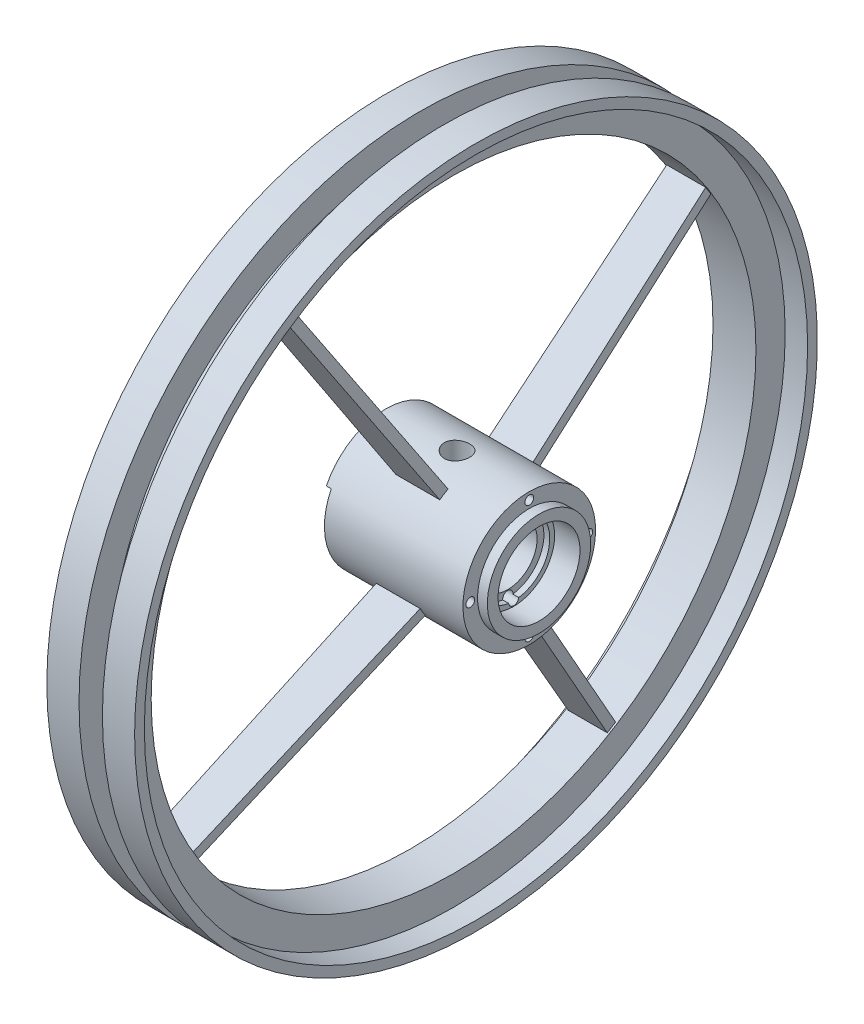
SolidWorks part; units mm, degrees
ref_plane "Front Plane" through (0, 0, 0) normal (0, 0, 1) x (1, 0, 0)
ref_plane "Top Plane" through (0, 0, 0) normal (0, 1, 0) x (1, 0, 0)
ref_plane "Right Plane" through (0, 0, 0) normal (1, 0, 0) x (0, 0, -1)
sketch "Sketch17" plane through (0, 0, 0) normal (0, 0, 1) x (1, 0, 0)
  line L0 (0, 0) -> (156.5215, 0) construction
sketch "Sketch1" plane through (0, 0, 0) normal (1, 0, 0) x (0, 0, -1)
  circle A0 centre (0, 0) radius 68
extrude "Boss-Extrude1" add sketch "Sketch1" along normal blind 157 contours A0
sketch "Sketch2" plane through (0, 0, 0) normal (-1, 0, 0) x (0, 0, 1)
  circle A0 centre (0, 0) radius 26
extrude "Cut-Extrude1" cut sketch "Sketch2" against normal up to next
sketch "Sketch3" plane through (0, 0, 0) normal (-1, 0, 0) x (0, 0, 1)
  line L1 (-68, 30) -> (68, 30)
  line L2 (-68, 30) -> (-68, -68)
  line L3 (-68, -68) -> (68, -68)
  line L4 (68, 30) -> (68, -68)
  circle A2 centre (0, 0) radius 68 construction
  circle A3 centre (0, 0) radius 26 construction
  dimension "D1" = 30
  dimension "D2" = 68
  dimension "D3" = 42
  dimension "D4" = 68
  dimension "D5" = 68
extrude "Cut-Extrude2" cut sketch "Sketch3" against normal blind 5 contours L2 L3 L4 L1
sketch "Sketch4" plane through (5, 0, 0) normal (-1, 0, 0) x (0, 0, 1)
  line L3 (-13.5, 29) -> (13.5, 29)
  arc A2 (13.5, 29) -> (-13.5, 29) centre (0, 0) cw
  dimension "D1" = 27
  dimension "D2" = 29
extrude "Cut-Extrude3" cut sketch "Sketch4" against normal blind 44
sketch "Sketch7" plane through (157, 0, 0) normal (1, 0, 0) x (0, 0, -1)
  circle A0 centre (0, 0) radius 42
extrude "Cut-Extrude4" cut sketch "Sketch7" against normal blind 26
sketch "Sketch8" plane through (131, 0, 0) normal (1, 0, 0) x (0, 0, -1)
  circle A0 centre (0, 0) radius 37
extrude "Cut-Extrude5" cut sketch "Sketch8" against normal blind 6 contours A0
sketch "Sketch9" plane through (125, 0, 0) normal (1, 0, 0) x (0, 0, -1)
  circle A0 centre (0, 0) radius 30
extrude "Cut-Extrude6" cut sketch "Sketch9" against normal blind 28 contours A0
ref_plane "Plane2" through (0, 0, 68) normal (0, 0, 1) x (1, 0, 0)
sketch "Sketch12" plane through (0, 0, 68) normal (0, 0, 1) x (1, 0, 0)
  line L0 (49, 37.9633) -> (49, -31.4216)
  line L1 (49, -31.4216) -> (59.8739, -42.2955)
  line L2 (59.8739, -42.2955) -> (85.8739, -42.2955)
  line L3 (85.8739, -42.2955) -> (97, -31.1695)
  line L4 (97, -31.1695) -> (97, 37.7112)
  line L5 (97, 37.7112) -> (85.8739, 48.8372)
  line L6 (85.8739, 48.8372) -> (59.8739, 48.8372)
  line L7 (59.8739, 48.8372) -> (49, 37.9633)
  line L8 (157, -68) -> (157, 68) construction
  line L9 (5, 30) -> (5, -68) construction
  dimension "D1" = 60
  dimension "D2" = 44
  dimension "D3" = 26
  dimension "D4" = 26
  dimension "D5" = 135
  dimension "D6" = 135
  dimension "D7" = 135
  dimension "D8" = 135
sketch "Sketch16" plane through (0, 0, 0) normal (-1, 0, 0) x (0, 0, 1)
  line L0 (35.9404, 57.726) -> (61.0246, 30) construction
  line L1 (35.9404, 57.726) -> (0, 68) construction
  arc A0 (61.0246, 30) -> (-61.0246, 30) centre (0, 0) ccw construction
  dimension "D1" = 37.38
  dimension "D2" = 37.3892
ref_plane "Plane5" through (0, 68, 0) normal (0, 1, 0) x (1, 0, 0)
ref_plane "Plane7" through (0, 0, 0) normal (0, 0, 1) x (1, 0, 0)
sketch "Sketch23" plane through (0, 68, 0) normal (0, 1, 0) x (1, 0, 0)
  line L0 (86, -40) -> (86, 40) construction
  point P9 (73, 0)
  dimension "D1" = 13
sketch "Sketch27" plane through (157, 0, 0) normal (1, 0, 0) x (0, 0, -1)
  circle A0 centre (0, 0) radius 68
  circle A1 centre (0, 0) radius 53
  dimension "D1" = 136
  dimension "D2" = 106
extrude "Cut-Extrude9" cut sketch "Sketch27" against normal blind 10
sketch "Sketch36" plane through (0, 0, 0) normal (0, 0, 1) x (1, 0, 0)
  line L0 (49, 29) -> (60, 40)
  line L1 (60, 40) -> (86, 40)
  line L2 (86, 40) -> (97, 29)
  line L8 (147, 68) -> (0, 68) construction
  line L17 (49, 29) -> (49, 0)
  line L18 (0, 0) -> (156.5215, 0) construction
  line L19 (49, 0) -> (97, 0)
  line L20 (97, 0) -> (97, 29)
  line L21 (157, -53) -> (157, 53) construction
  line L22 (5, 30) -> (5, -68) construction
  dimension "D1" = 60
  dimension "D2" = 44
  dimension "D3" = 135
  dimension "D4" = 40
  dimension "D5" = 26
revolve "Cut-Revolve2" cut sketch "Sketch36" angle 360 about L0
hole_wizard "Tap Drill for M1.2x0.25 Tap1" positions "Sketch23" profile "Sketch26" hole size "M1.2x0.25" standard "ISO"
sketch "Sketch26" plane through (73, 68, 0) normal (1, 0, 0) x (0, 0, 1)
  line L0 (0, 0) -> (0, 68)
  line L1 (0, 68) -> (13, 68)
  line L2 (13, 68) -> (13, 0)
  line L5 (13, 0) -> (0, 0)
  line L10 (0, 68) -> (-13, 68) construction
  line L11 (0, -6.35) -> (0, 107.95) construction
  dimension "Hole Dia." = 26
  dimension "Hole Depth" = 68
  dimension "Drill Angle" = 180
sketch "Sketch29" plane through (147, 0, 0) normal (1, 0, 0) x (0, 0, -1)
  line L0 (0, 68) -> (0, 53) construction
  line L1 (53, 0) -> (68, 0) construction
  line L2 (0, -53) -> (0, -68) construction
  line L3 (-53, 0) -> (-68, 0) construction
  line L4 (-68, 74.8) -> (-68, -74.8) construction
  circle A0 centre (0, 0) radius 53 construction
  circle A1 centre (0, 0) radius 53 construction
  circle A2 centre (0, 0) radius 68 construction
  point P21 (0, 60.5)
  point P23 (60.5, 0)
  point P25 (0, -60.5)
  point P27 (-60.5, 0)
hole_wizard "M8 Clearance Hole1" positions "Sketch29" profile "Sketch30" hole size "M8" standard "ISO"
sketch "Sketch30" plane through (147, 0, 60.5) normal (0, 1, 0) x (0, 0, -1)
  line L0 (0, 0) -> (0, 37.7039)
  line L1 (0, 37.7039) -> (4.5, 35)
  line L2 (4.5, 35) -> (4.5, 0)
  line L5 (4.5, 0) -> (0, 0)
  line L10 (0, 37.7039) -> (-4.5, 35) construction
  line L11 (0, -6.35) -> (0, 107.95) construction
  dimension "Hole Dia." = 9
  dimension "Hole Depth" = 35
  dimension "Drill Angle" = 118
ref_plane "Plane4" through (0, 0, 0) normal (0, 0.5285, -0.8489) x (-1, 0, 0)
sketch "Sketch19" plane through (0, 0, 0) normal (0, 0.5285, -0.8489) x (-1, 0, 0)
  line L1 (-97, 30) -> (-97, -30) construction
  line L3 (-27.3689, 310) -> (-67.3689, 310)
  line L9 (0, 0) -> (-156.5215, 0) construction
  line L10 (-67.3689, 310) -> (-95.5, 66.5)
  line L11 (-95.5, 66.5) -> (-50.5, 66.5)
  line L12 (-50.5, 66.5) -> (-27.3689, 310)
  line L13 (0, 68) -> (-147, 68) construction
  dimension "D1" = 310
  dimension "D2" = 83.41
  dimension "D3" = 45
  dimension "D4" = 1.5
  dimension "D5" = 1.5
  dimension "D6" = 40
sketch "Sketch21" plane through (0, 0, 0) normal (0, 0.5285, -0.8489) x (-1, 0, 0)
  line L0 (-67.3689, 310) -> (-69.3689, 310)
  line L1 (-69.3689, 310) -> (-69.3689, 340)
  line L2 (-69.3689, 340) -> (-92.3689, 340)
  line L3 (-92.3689, 340) -> (-92.3689, 350)
  line L4 (-92.3689, 350) -> (-59.3689, 350)
  line L5 (-2.3689, 350) -> (-2.3689, 340)
  line L6 (-2.3689, 340) -> (-25.3689, 340)
  line L7 (-25.3689, 340) -> (-25.3689, 310)
  line L8 (-25.3689, 310) -> (-27.3689, 310)
  line L11 (-59.3689, 350) -> (-59.3689, 320)
  line L12 (-59.3689, 320) -> (-35.3689, 320)
  line L13 (-35.3689, 320) -> (-35.3689, 350)
  line L14 (-35.3689, 350) -> (-2.3689, 350)
  line L15 (-27.3689, 310) -> (-67.3689, 310) construction
  line L17 (-67.3689, 310) -> (-27.3689, 310)
  dimension "D2" = 10
  dimension "D3" = 10
  dimension "D7" = 10
  dimension "D8" = 90
  dimension "D11" = 40
  dimension "D12" = 40
  dimension "D10" = 2
  dimension "D5" = 2
  dimension "D6" = 10
  dimension "D9" = 10
  dimension "D4" = 23
  dimension "D13" = 24
revolve "Revolve1" add sketch "Sketch21" angle 360 about L0
extrude "Boss-Extrude4" add sketch "Sketch19" along normal mid plane 10
pattern_circular "CirPattern4" count 4 every 90 about axis through (0, 0, 0) along (1, 0, 0) of "Boss-Extrude4"
sketch "Esquisse4" plane through (131, 0, 0) normal (1, 0, 0) x (0, 0, -1)
  line L0 (0, 0) -> (0, -36) construction
  point P11 (0, -36)
  dimension "D1" = 36
  dimension "D2" = 0
hole_wizard "M10 Clearance Hole1" positions "Esquisse4" profile "Esquisse6" hole size "M10" standard "ANSI Metric"
sketch "Esquisse6" plane through (131, -36, 0) normal (0, 1, 0) x (0, 0, -1)
  line L0 (0, 0) -> (0, 15)
  line L1 (0, 15) -> (5.25, 15)
  line L2 (5.25, 15) -> (5.25, 0)
  line L5 (5.25, 0) -> (0, 0)
  line L10 (0, 15) -> (-5.25, 15) construction
  line L11 (0, -6.35) -> (0, 107.95) construction
  dimension "Hole Dia." = 10.5
  dimension "Hole Depth" = 15
  dimension "Drill Angle" = 180
equation "\"D1@Sketch3\"=26+8/2"
equation "\"D2@Sketch3\"=26+\"D3@Sketch3\""
equation "\"D4@Sketch3\"=\"D2@Sketch3\""
equation "\"D5@Sketch3\"=\"D2@Sketch3\""
equation "\"D12@Sketch21\"=\"D11@Sketch21\""
equation "\"D2@Sketch27\"=\"D1@Sketch27\"-15*2"
equation "\"D4@Sketch21\"=(\"D8@Sketch21\"-\"D6@Sketch21\"-\"D13@Sketch21\"-\"D9@Sketch21\")/2"
